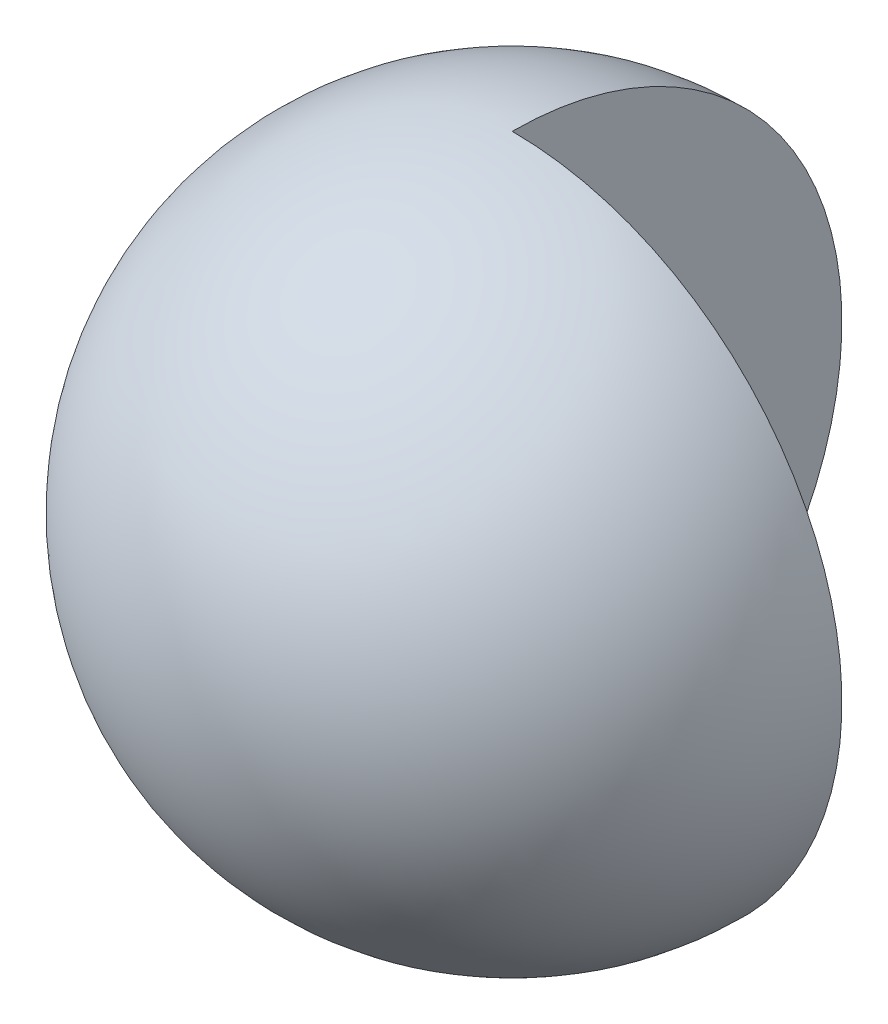
SolidWorks part; units mm, degrees
ref_plane "Front Plane" through (0, 0, 0) normal (0, 0, 1) x (1, 0, 0)
ref_plane "Top Plane" through (0, 0, 0) normal (0, 1, 0) x (1, 0, 0)
ref_plane "Right Plane" through (0, 0, 0) normal (1, 0, 0) x (0, 0, -1)
sketch "Sketch1" plane through (0, 0, 0) normal (0, 0, 1) x (1, 0, 0)
  line L0 (0, 29.8544) -> (0, -29.8544) construction
  line L1 (0, 29.8544) -> (0, -29.8544)
  arc A0 (0, -29.8544) -> (0, 29.8544) centre (0, 0) ccw
ref_axis "Axis1" through (0, -32.8398, 0) along (0, 1, 0)
revolve "Revolve4" add sketch "Sketch1" angle 270 about L0
